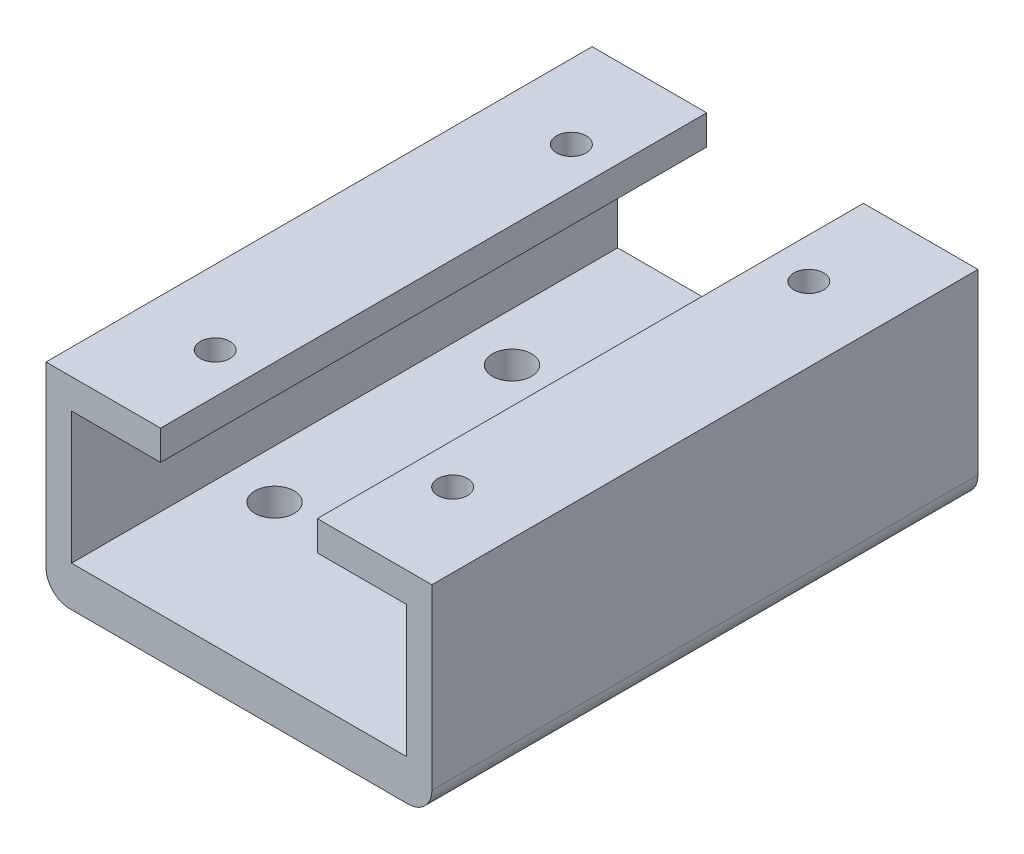
SolidWorks part; units mm, degrees
ref_plane "前视基准面" through (0, 0, 0) normal (0, 0, 1) x (1, 0, 0)
ref_plane "上视基准面" through (0, 0, 0) normal (0, 1, 0) x (1, 0, 0)
ref_plane "右视基准面" through (0, 0, 0) normal (1, 0, 0) x (0, 0, -1)
sketch "草图1" plane through (0, 0, 0) normal (0, 1, 0) x (1, 0, 0)
  line L1 (16.25, -23) -> (-16.25, -23)
  line L2 (16.25, -23) -> (16.25, 23)
  line L3 (16.25, 23) -> (-16.25, 23)
  line L4 (-16.25, -23) -> (-16.25, 23)
  line L5 (16.25, -23) -> (-16.25, 23) construction
  line L6 (16.25, 23) -> (-16.25, -23) construction
  point P0 (0, 0)
  dimension "D1" = 32.5
  dimension "D2" = 46
extrude "凸台-拉伸1" add sketch "草图1" along normal blind 17
sketch "草图2" plane through (0, 0, -23) normal (0, 0, -1) x (-1, 0, 0)
  line L0 (-16.25, 17) -> (16.25, 17) construction
  line L1 (-6.6, 14.5) -> (6.6, 14.5)
  line L2 (-6.6, 14.5) -> (-6.6, 17)
  line L3 (-6.6, 17) -> (6.6, 17)
  line L4 (6.6, 14.5) -> (6.6, 17)
  line L5 (-6.6, 14.5) -> (6.6, 17) construction
  line L6 (-6.6, 17) -> (6.6, 14.5) construction
  line L8 (-14.1, 3.4) -> (14.1, 3.4)
  line L9 (-14.1, 3.4) -> (-14.1, 14.5)
  line L10 (-14.1, 14.5) -> (14.1, 14.5)
  line L11 (14.1, 3.4) -> (14.1, 14.5)
  line L12 (-14.1, 3.4) -> (14.1, 14.5) construction
  line L13 (-14.1, 14.5) -> (14.1, 3.4) construction
  point P0 (0, 15.75)
  point P9 (0, 8.95)
  line M7 (16.25, 17) -> (-16.25, 17)
  dimension "D1" = 2.5
  dimension "D2" = 13.2
  dimension "D3" = 28.2
  dimension "D4" = 13.6
  dimension "D5" = 0
extrude "切除-拉伸2" cut sketch "草图2" against normal through all contours L1 L4 L2 M7 | L8 L11 L10 L1 L9 region at (0, 15.75, -23) region at (0, 8.95, -23)
sketch "草图4" plane through (0, 0, 0) normal (0, -1, 0) x (1, 0, 0)
  line L1 (-10, -10) -> (10, -10) construction
  line L2 (-10, -10) -> (-10, 10) construction
  line L3 (-10, 10) -> (10, 10) construction
  line L4 (10, -10) -> (10, 10) construction
  line L5 (-10, -10) -> (10, 10) construction
  line L6 (-10, 10) -> (10, -10) construction
  circle A0 centre (-10, 10) radius 1.65
  circle A1 centre (10, 10) radius 1.65
  circle A2 centre (10, -10) radius 1.65
  circle A3 centre (-10, -10) radius 1.65
  point P0 (0, 0)
  dimension "D3" = 3.3
  dimension "D4" = 3.3
  dimension "D5" = 3.3
  dimension "D6" = 3.3
  dimension "D1" = 20
  dimension "D2" = 20
extrude "切除-拉伸3" cut sketch "草图4" against normal up to next
sketch "草图5" plane through (0, 17, 0) normal (0, 1, 0) x (1, 0, 0)
  line L1 (-10, -15) -> (10, -15) construction
  line L2 (-10, -15) -> (-10, 15) construction
  line L3 (-10, 15) -> (10, 15) construction
  line L4 (10, -15) -> (10, 15) construction
  line L5 (-10, -15) -> (10, 15) construction
  line L6 (-10, 15) -> (10, -15) construction
  circle A0 centre (-10, 15) radius 1.25
  circle A1 centre (10, 15) radius 1.25
  circle A2 centre (10, -15) radius 1.25
  circle A3 centre (-10, -15) radius 1.25
  point P0 (0, 0)
  dimension "D3" = 2.5
  dimension "D4" = 2.5
  dimension "D5" = 2.5
  dimension "D6" = 2.5
  dimension "D1" = 30
  dimension "D2" = 20
extrude "切除-拉伸4" cut sketch "草图5" against normal blind 2
fillet "圆角1" radius 2 2 edges at (16.25, 0, 0) (-16.25, 0, 0)
equation "\"33.5.00mm\"=34"
